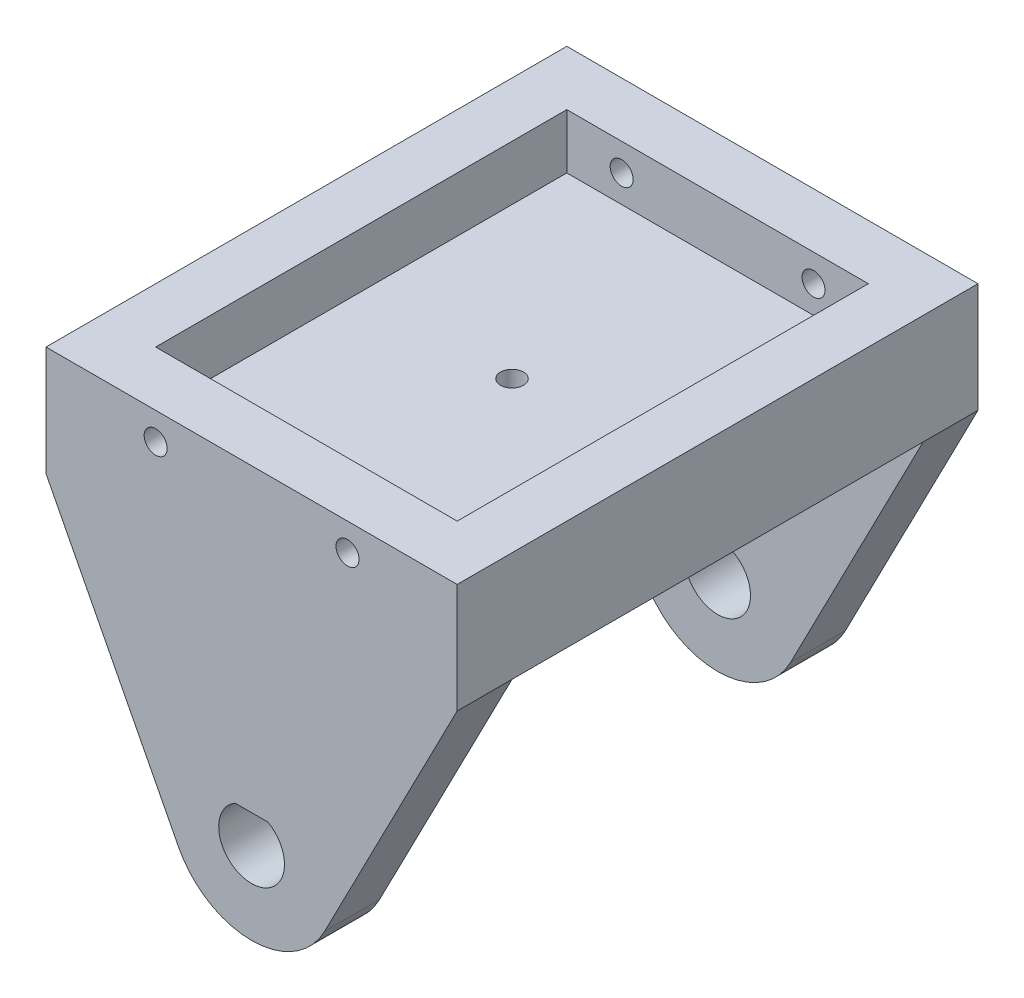
SolidWorks part; units mm, degrees
ref_plane "Front Plane" through (0, 0, 0) normal (0, 0, 1) x (1, 0, 0)
ref_plane "Top Plane" through (0, 0, 0) normal (0, 1, 0) x (1, 0, 0)
ref_plane "Right Plane" through (0, 0, 0) normal (1, 0, 0) x (0, 0, -1)
sketch "Sketch1" plane through (0, 0, 0) normal (0, 0, 1) x (1, 0, 0)
  line L0 (-3, 5.1962) -> (3, 5.1962)
  line L1 (-37.5, 40) -> (37.5, 40)
  line L2 (-13.3322, -6.874) -> (-37.5, 40)
  line L3 (13.3322, -6.874) -> (37.5, 40)
  line L4 (-37.5, 40) -> (-37.5, 60)
  line L5 (-37.5, 60) -> (37.5, 60)
  line L6 (37.5, 60) -> (37.5, 40)
  circle A0 centre (0, 0) radius 15
  circle A1 centre (0, 0) radius 6
  dimension "D1" = 30
  dimension "D2" = 12
  dimension "D3" = 6
  dimension "D4" = 40
  dimension "D5" = 75
  dimension "D7" = 20
extrude "Boss-Extrude1" add sketch "Sketch1" against normal blind 10 contours A0 L3 L1 L2 | A0 A1 | L0 A1 region at (0, 5.5196, 0) region at (0, 25.531, 0) region at (-3.4367, 14.1648, 0)
extrude "Boss-Extrude2" add sketch "Sketch1<3>" against normal blind 95 contours L6 L5 L4 L1 region at (0, 50, 0)
sketch "Sketch1<3>" plane through (0, 0, 0) normal (0, 0, 1) x (1, 0, 0) same geometry as "Sketch1"
sketch "Sketch6" plane through (0, 40, 0) normal (0, -1, 0) x (-1, 0, 0)
  line L0 (37.5, 47.5) -> (-37.5, 47.5) construction
  line L1 (37.5, 95) -> (37.5, 10) construction
  line L2 (-37.5, 95) -> (-37.5, 10) construction
  line L3 (37.5, 95) -> (-37.5, 95) construction
  line L4 (-37.5, 47.5) -> (37.5, 47.5) construction
  dimension "D1" = 47.5
sketch "Sketch7" plane through (0, 60, 0) normal (0, 1, 0) x (1, 0, 0)
  line L0 (-37.5, 47.5) -> (37.5, 47.5) construction
  line L1 (-37.5, 95) -> (-37.5, 0) construction
ref_plane "Plane2" through (0, 0, -47.5) normal (0, 0, 1) x (1, 0, 0)
mirror "Mirror2" about plane through (0, 0, -47.5) normal (0, 0, 1) of "Boss-Extrude1"
sketch "Sketch8" plane through (0, 60, 0) normal (0, 1, 0) x (1, 0, 0)
  line L0 (-37.5, 0) -> (37.5, 0) construction
  line L1 (-27.5, 85) -> (27.5, 85)
  line L2 (-27.5, 85) -> (-27.5, 10)
  line L3 (-27.5, 10) -> (27.5, 10)
  line L4 (27.5, 85) -> (27.5, 10)
  line L5 (37.5, 95) -> (37.5, 0) construction
  line L7 (-37.5, 95) -> (-37.5, 0) construction
  line L8 (-37.5, 95) -> (37.5, 95) construction
  dimension "D1" = 10
  dimension "D2" = 10
  dimension "D3" = 10
  dimension "D4" = 10
extrude "Cut-Extrude2" cut sketch "Sketch8" against normal blind 10
sketch "Sketch9" plane through (0, 0, 0) normal (0, 0, 1) x (1, 0, 0)
  line L0 (0, 60) -> (0, 40) construction
  line L1 (-37.5, 60) -> (37.5, 60) construction
  line L2 (-37.5, 40) -> (37.5, 40) construction
  line L3 (-37.5, 55) -> (37.5, 55) construction
  line L4 (-37.5, 40) -> (-37.5, 60) construction
  line L5 (37.5, 60) -> (37.5, 40) construction
  circle A0 centre (-17.5, 55) radius 2
  circle A1 centre (17.5, 55) radius 2
  point P12 (-17.5, 55)
  point P14 (17.5, 55)
  dimension "D2" = 4
  dimension "D3" = 17.5
  dimension "D1" = 5
hole_wizard "Tap Drill for M5x0.8 Tap2" positions "Sketch11" profile "Sketch12" hole size "M5x0.8" standard "ANSI Metric" end condition through all
sketch "Sketch11" plane through (0, 0, 0) normal (0, 0, 1) x (1, 0, 0)
  point P0 (-17.5, 55)
  point P3 (17.5, 55)
sketch "Sketch12" plane through (-17.5, 55, 0) normal (1, 0, 0) x (0, -1, 0)
  line L0 (0, 0) -> (0, 95)
  line L1 (0, 95) -> (2.1, 95)
  line L2 (2.1, 95) -> (2.1, 0)
  line L5 (2.1, 0) -> (0, 0)
  line L11 (0, -6.35) -> (0, 107.95) construction
  dimension "Thru Hole Dia." = 4.2
  dimension "Thru Hole Depth" = 95
sketch "Sketch13" plane through (0, 50, 0) normal (0, 1, 0) x (1, 0, 0)
  line L0 (-27.5, 47.5) -> (27.5, 47.5) construction
  line L1 (-27.5, 85) -> (-27.5, 10) construction
  line L2 (27.5, 10) -> (27.5, 85) construction
  point P8 (0, 47.5)
hole_wizard "Tap Drill for M5x0.8 Tap3" positions "Sketch14" profile "Sketch16" hole size "M5x0.8" standard "ANSI Metric"
sketch "Sketch14" plane through (0, 50, 0) normal (0, 1, 0) x (1, 0, 0)
  point P0 (0, 47.5)
sketch "Sketch16" plane through (0, 50, -47.5) normal (1, 0, 0) x (0, 0, 1)
  line L0 (0, 0) -> (0, 11.2618)
  line L1 (0, 11.2618) -> (2.1, 10)
  line L2 (2.1, 10) -> (2.1, 0)
  line L5 (2.1, 0) -> (0, 0)
  line L10 (0, 11.2618) -> (-2.1, 10) construction
  line L11 (0, -6.35) -> (0, 107.95) construction
  dimension "Hole Dia." = 4.2
  dimension "Hole Depth" = 10
  dimension "Drill Angle" = 118
